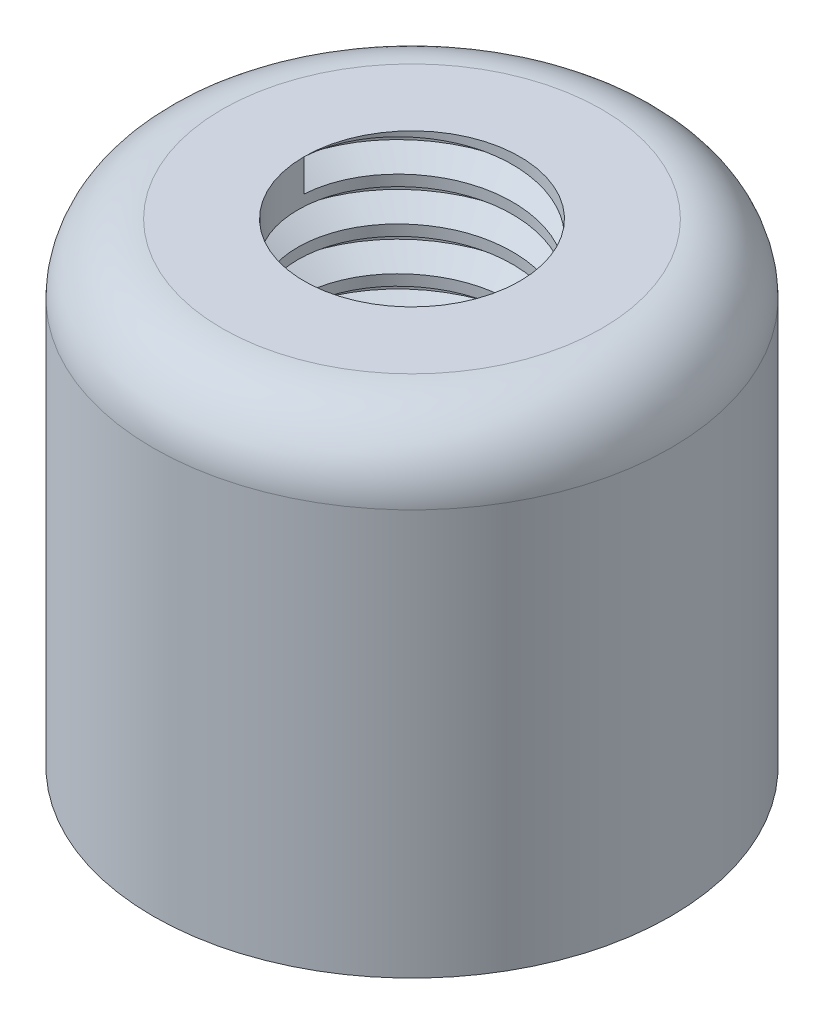
SolidWorks part; units mm, degrees
material "1023 Carbon Steel Sheet (SS)"
ref_plane "Płaszczyzna przednia" through (0, 0, 0) normal (0, 0, 1) x (1, 0, 0)
ref_plane "Płaszczyzna górna" through (0, 0, 0) normal (0, 1, 0) x (1, 0, 0)
ref_plane "Płaszczyzna prawa" through (0, 0, 0) normal (1, 0, 0) x (0, 0, -1)
sketch "Szkic1" plane through (0, 0, 0) normal (0, 1, 0) x (1, 0, 0)
  circle A0 centre (0, 0) radius 3
  dimension "D1" = 6
extrude "Dodanie-wyciągnięcie1" add sketch "Szkic1" along normal blind 5.5
sketch "Szkic2" plane through (0, 5.5, 0) normal (0, 1, 0) x (1, 0, 0)
  circle A0 centre (0, 0) radius 1.25
  dimension "D1" = 2.5
extrude "Wytnij-wyciągnięcie1" cut sketch "Szkic2" against normal blind 5
fillet "Zaokrąglenie1" radius 0.8 1 edges at (0, 5.5, 3)
thread "Gwint1" pitch 0.5 method cut profile "Profil gwintu1" start angle 0, offset 0, length 5, pitch 0.5, diameter 2.5
ref_plane "Płaszczyzna1" through (-1.25, 5.5, 0) normal (0, 0, 1) x (-1, 0, 0)
sketch "Profil gwintu1" plane through (-1.25, 5.5, 0) normal (0, 0, 1) x (-1, 0, 0)
  line L0 (0, 0) -> (0, 0.5) construction
  line L1 (0, 0) -> (0.2706, 0.1562)
  line L2 (0.2706, 0.1562) -> (0.2706, 0.2187)
  line L3 (0.2706, 0.2187) -> (0, 0.375)
  line L4 (0.2706, 0.1875) -> (0, 0.1875) construction
  line L11 (0, 0) -> (0, 0.375)
  point P2 (0, 0)
  dimension "Pitch" = 0.5
  dimension "Profile_Angle" = 60
  dimension "Profile_Land" = 0.0625
  dimension "Profile_Height" = 0.2706
